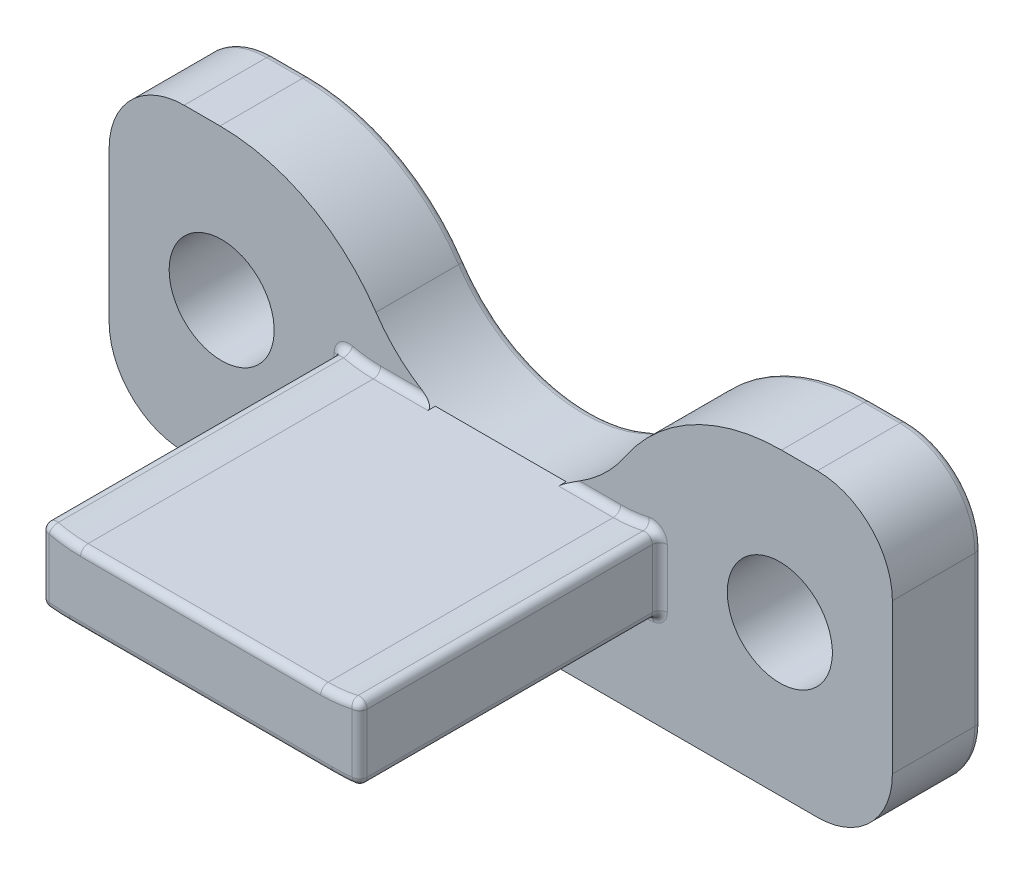
SolidWorks part; units mm, degrees
ref_plane "Front Plane" through (0, 0, 0) normal (0, 0, 1) x (1, 0, 0)
ref_plane "Top Plane" through (0, 0, 0) normal (0, 1, 0) x (1, 0, 0)
ref_plane "Right Plane" through (0, 0, 0) normal (1, 0, 0) x (0, 0, -1)
sketch "Sketch1" plane through (0, 0, 0) normal (0, 0, 1) x (1, 0, 0)
  line L0 (-13.2588, 0) -> (13.2588, 0) construction
  line L1 (-13.2588, -5.08) -> (13.2588, -5.08)
  line L2 (-13.2588, -5.08) -> (-13.2588, 5.08)
  line L3 (-13.2588, 5.08) -> (13.2588, 5.08)
  line L4 (13.2588, -5.08) -> (13.2588, 5.08)
  line L5 (-13.2588, -5.08) -> (13.2588, 5.08) construction
  line L6 (-13.2588, 5.08) -> (13.2588, -5.08) construction
  circle A0 centre (-9.4488, 0) radius 1.778
  circle A1 centre (9.4488, 0) radius 1.778
  point P0 (0, 0)
  dimension "D1" = 3.556
  dimension "D2" = 3.556
  dimension "D3" = 18.8976
  dimension "D4" = 3.81
  dimension "D5" = 3.81
  dimension "D6" = 5.08
extrude "Boss-Extrude1" add sketch "Sketch1" along normal blind 3.048
sketch "Sketch3" plane through (0, 0, 3.048) normal (0, 0, 1) x (1, 0, 0)
  line L0 (13.2588, 5.08) -> (-13.2588, 5.08) construction
  circle A0 centre (0, 5.08) radius 5.08
  dimension "D1" = 10.16
extrude "Cut-Extrude1" cut sketch "Sketch3" against normal through all
fillet "Fillet1" radius 6.35 2 edges at (-5.08, 5.08, 1.524) (5.08, 5.08, 1.524)
sketch "Sketch4" plane through (0, 0, 3.048) normal (0, 0, 1) x (1, 0, 0)
  line L0 (0, 5.08) -> (0, -5.08) construction
  line L1 (-13.2588, -5.08) -> (13.2588, -5.08) construction
  line L2 (0, -5.08) -> (0, 5.08) construction
  line L3 (-4.064, 4.953) -> (4.064, 4.953) construction
  line L4 (-4.064, 9.398) -> (4.064, 9.398)
  line L5 (-4.064, 0.508) -> (4.064, 0.508)
  line L6 (0, 5.08) -> (0, 11.3682) construction
  line L7 (0, 11.3682) -> (0, 5.08) construction
  line L8 (-9.5038, 5.08) -> (-13.2588, 5.08) construction
  line L9 (-4.445, 4.953) -> (4.445, 4.953) construction
  line L10 (-4.445, 11.811) -> (4.445, 11.811)
  line L11 (-4.445, -1.905) -> (4.445, -1.905)
  arc A0 (-4.064, 9.398) -> (-4.064, 0.508) centre (-4.064, 4.953) ccw
  arc A1 (4.064, 0.508) -> (4.064, 9.398) centre (4.064, 4.953) ccw
  arc A2 (-4.445, 11.811) -> (-4.445, -1.905) centre (-4.445, 4.953) ccw
  arc A3 (4.445, -1.905) -> (4.445, 11.811) centre (4.445, 4.953) ccw
  point P7 (0, 4.953)
  point P12 (0, 4.953)
  point P23 (0, 0)
  point P24 (0, 0)
  dimension "D4" = 6.858
  dimension "D1" = 8.128
  dimension "D2" = 8.89
  dimension "D3" = 4.318
  dimension "D5" = 8.89
extrude "Boss-Extrude2" add sketch "Sketch4" along normal blind 10.16
sketch "Sketch5" plane through (0, 0, 13.208) normal (0, 0, 1) x (1, 0, 0)
  line L1 (-11.303, 5.08) -> (11.3122, 5.08)
  line L2 (-11.303, 5.08) -> (-11.303, 12.0504)
  line L3 (-11.303, 12.0504) -> (11.3122, 12.0504)
  line L4 (11.3122, 5.08) -> (11.3122, 12.0504)
  line L6 (13.2588, 5.08) -> (11.3018, 5.08) construction
  point P4 (0, 0)
  dimension "D1" = 22.6152
  dimension "D2" = 6.9704
  dimension "D3" = 6.9704
extrude "Cut-Extrude2" cut sketch "Sketch5" against normal blind 10.16
sketch "Sketch7" plane through (0, 0, 0) normal (0, 0, -1) x (-1, 0, 0)
  circle A0 centre (-9.4488, 0) radius 1.778
  circle A1 centre (9.4488, 0) radius 1.778
  arc A2 (-7.9432, -0.9457) -> (-10.3791, 1.5152) centre (-9.4488, 0) ccw construction
extrude "Cut-Extrude3" cut sketch "Sketch7" against normal through all
sketch "Sketch8" plane through (0, 0, 13.208) normal (0, 0, 1) x (1, 0, 0)
  line L1 (-5.3848, -2.0203) -> (-13.0339, -2.0203)
  line L2 (-5.3848, -2.0203) -> (-5.3848, 6.2499)
  line L3 (-5.3848, 6.2499) -> (-13.0339, 6.2499)
  line L4 (-13.0339, -2.0203) -> (-13.0339, 6.2499)
  line L5 (5.3848, -2.216) -> (12.961, -2.216)
  line L6 (5.3848, -2.216) -> (5.3848, 6.7587)
  line L7 (5.3848, 6.7587) -> (12.961, 6.7587)
  line L8 (12.961, -2.216) -> (12.961, 6.7587)
  circle A1 centre (-9.4488, 0) radius 1.778 construction
  arc A3 (10.3791, 1.5152) -> (7.9432, -0.9457) centre (9.4488, 0) ccw construction
  dimension "D1" = 2.286
  dimension "D3" = 7.6491
  dimension "D5" = 2.286
extrude "Cut-Extrude4" cut sketch "Sketch8" against normal blind 10.16
fillet "Fillet2" radius 2.54 4 edges at (13.2588, 5.08, 1.524) (13.2588, -5.08, 1.524) (-13.2588, -5.08, 1.524) (-13.2588, 5.08, 1.524)
fillet "Fillet3" radius 0.254 35 edges at (3.1392, 0.508, 3.048) (-3.1392, 0.508, 3.048) (4.732, 0.5585, 3.048) (-4.732, 0.5585, 3.048) (5.3848, 0.7088, 8.128) (5.3848, -0.5658, 3.048) (-5.3848, -0.5658, 3.048) (-5.3848, 0.7088, 8.128) (-4.732, 0.5585, 13.208) (0, 0.508, 13.208) (4.732, 0.5585, 13.208) (5.3848, -0.5658, 13.208) (-5.3848, -0.5658, 13.208) (11.2268, 0, 0) (-7.6708, 0, 0) (6.5104, 4.3302, 0) (0, 0, 0) (-6.5104, 4.3302, 0) (-10.1113, 5.08, 0) (-12.5149, 4.3361, 0) (-13.2588, 0, 0) (-12.5149, -4.3361, 0) (0, -5.08, 0) (12.5149, -4.3361, 0) (13.2588, 0, 0) (12.5149, 4.3361, 0) (10.1113, 5.08, 0) (4.916, -1.8888, 13.208) (5.3848, -1.8403, 8.128) (4.916, -1.8888, 3.048) (-4.916, -1.8888, 3.048) (-5.3848, -1.8403, 8.128) (-4.916, -1.8888, 13.208) (0, -1.905, 13.208) (0, -1.905, 3.048)
